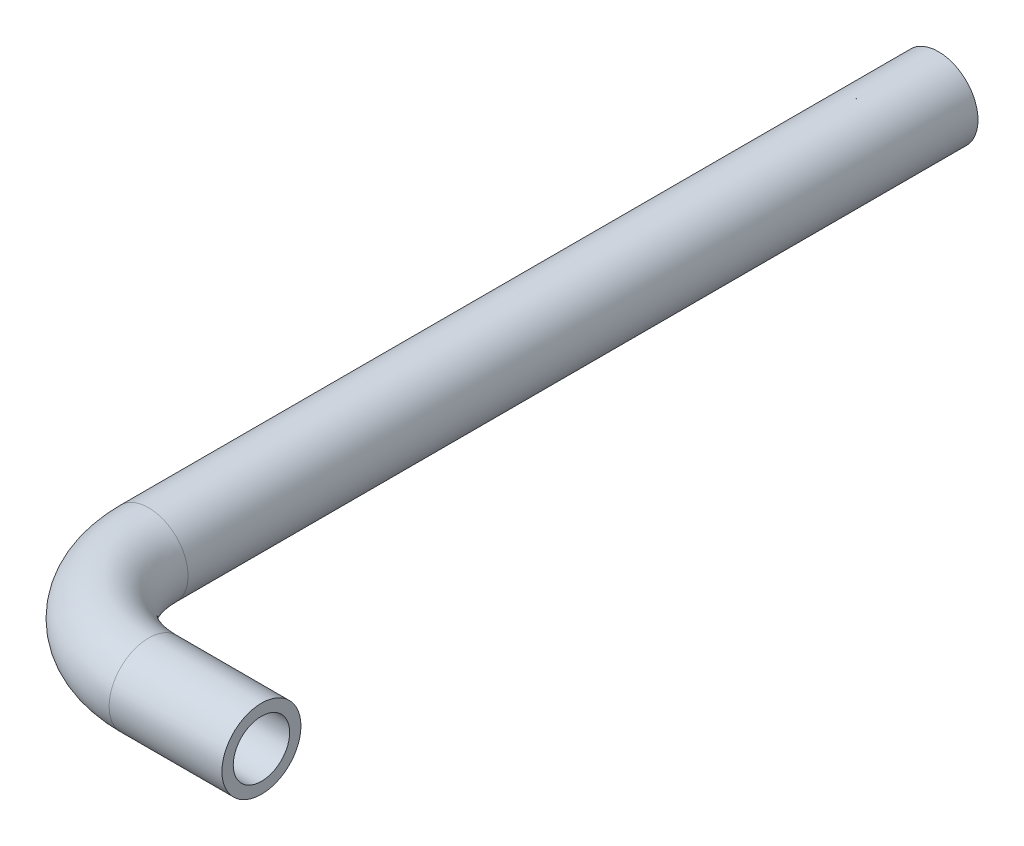
SolidWorks part; units mm, degrees
ref_plane "前视基准面" through (0, 0, 0) normal (0, 0, 1) x (1, 0, 0)
ref_plane "上视基准面" through (0, 0, 0) normal (0, 1, 0) x (1, 0, 0)
ref_plane "右视基准面" through (0, 0, 0) normal (1, 0, 0) x (0, 0, -1)
sketch "草图1" plane through (0, 0, 0) normal (1, 0, 0) x (0, 0, -1)
  circle A0 centre (0, 0) radius 12.5
  circle A1 centre (0, 0) radius 17.5
sketch "草图2" plane through (0, 0, 0) normal (0, 1, 0) x (1, 0, 0)
  line L0 (0, 0) -> (-450, 0)
  line L1 (-500, 50) -> (-500, 400)
  arc A0 (-450, 0) -> (-500, 50) centre (-450, 50) cw
  dimension "D1" = 50
sweep "扫描1" add profiles "草图1" path "草图2"
ref_plane "基准面1" through (-250, 0, 0) normal (1, 0, 0) x (0, 0, -1)
sketch "草图3" plane through (-250, 0, 0) normal (1, 0, 0) x (0, 0, -1)
  circle A0 centre (0, 0) radius 12.5
  circle A1 centre (0, 0) radius 17.5
ref_plane "基准面2" through (-150, 0, 0) normal (1, 0, 0) x (0, 0, -1)
extrude "切除-拉伸3" cut sketch "草图3" along normal up to next and the other way blind 150
